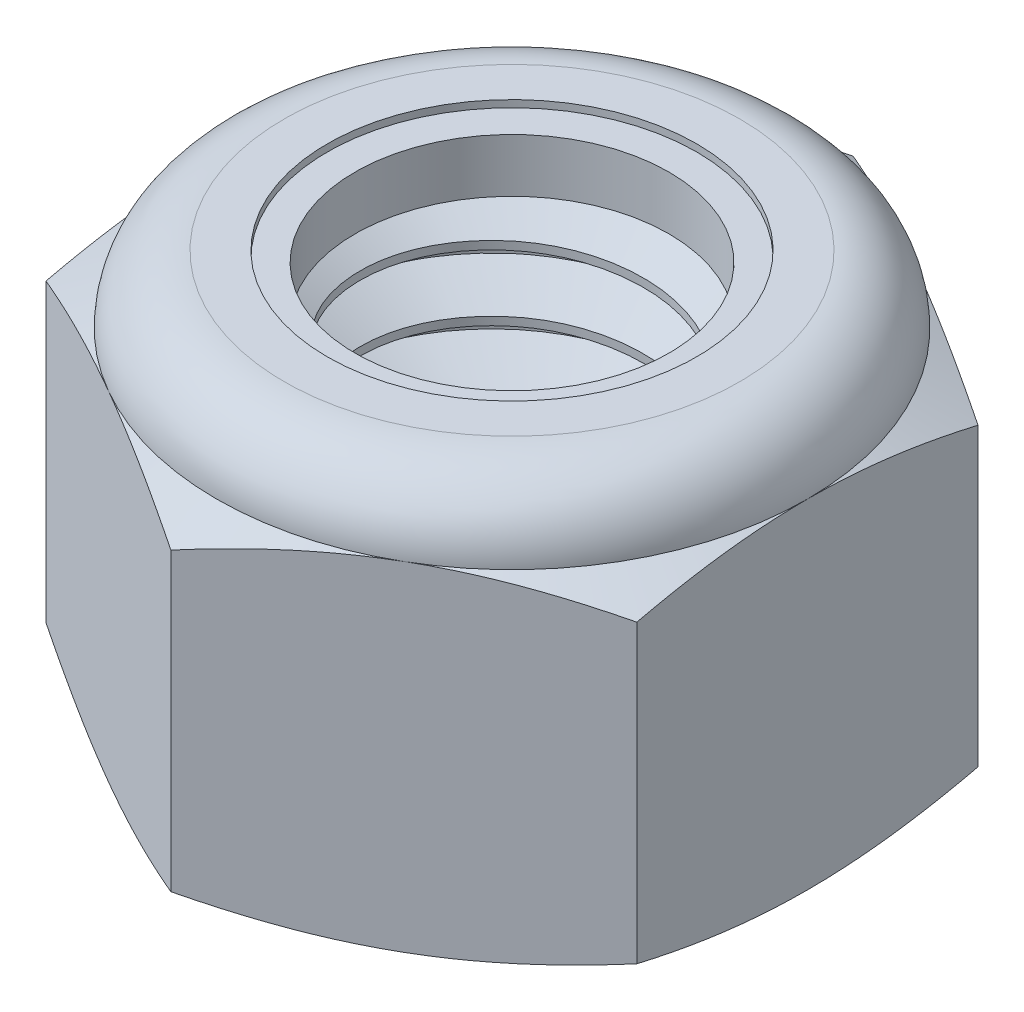
SolidWorks part; units mm, degrees
note: '?' marks a value the reader was unsure of.
ref_plane "Front" through (0, 0, 0) normal (0, 0, 1) x (1, 0, 0)
ref_plane "Top" through (0, 0, 0) normal (0, 1, 0) x (1, 0, 0)
ref_plane "Right" through (0, 0, 0) normal (1, 0, 0) x (0, 0, -1)
sketch "Sketch8" plane through (0, 0, 0) normal (1, 0, 0) x (0, 0, -1)
  line L0 (0, 0) -> (0, 8.7312) construction
  line L1 (6.35, 0) -> (-6.35, 0) construction
  line L2 (-3.9688, 8.7312) -> (3.9688, 8.7312) construction
  line L3 (3.9688, 8.7312) -> (3.9688, 7.3201) construction
sketch "Sketch1" plane through (0, 0, 0) normal (0, 1, 0) x (1, 0, 0)
  line L1 (0, 7.3323) -> (-6.35, 3.6662)
  line L2 (-6.35, 3.6662) -> (-6.35, -3.6662)
  line L3 (-6.35, -3.6662) -> (0, -7.3323)
  line L4 (0, -7.3323) -> (6.35, -3.6662)
  line L5 (6.35, -3.6662) -> (6.35, 3.6662)
  line L6 (6.35, 3.6662) -> (0, 7.3323)
  circle A0 centre (0, 0) radius 6.35 construction
  circle A1 centre (0, 0) radius 3.9688
extrude "Extrude1" add sketch "Sketch1" along normal up to vertex (8.7312 mm away) up to point (0, 8.7312, 0)
sketch "Sketch5" plane through (0, 0, 0) normal (1, 0, 0) x (0, 0, -1)
  line L0 (0, 0) -> (6.35, 0)
  line L1 (6.35, 0) -> (7.3323, 0.4581)
  line L2 (7.3323, 0.4581) -> (7.3323, 6.818)
  line L3 (7.3323, 6.818) -> (6.35, 7.276)
  line L4 (4.8948, 8.7312) -> (4.8948, 10.0012)
  line L5 (4.8948, 10.0012) -> (8.6023, 10.0012)
  line L6 (8.6023, 10.0012) -> (8.6023, -1.27)
  line L7 (8.6023, -1.27) -> (0, -1.27)
  line L8 (0, -1.27) -> (0, 0)
  line L9 (6.35, 7.276) -> (6.35, 0) construction
  line L12 (7.3323, 8.7312) -> (7.3323, 0) construction
  line L13 (7.3323, 4.3656) -> (8.6023, 4.3656) construction
  line L15 (0, 0) -> (0, 10.0012) construction
  line L18 (6.35, 0) -> (-6.35, 0) construction
  line L19 (3.6662, 8.7312) -> (7.3323, 8.7312) construction
  line L20 (0, 10.0012) -> (4.8948, 10.0012) construction
  line L21 (3.6662, 0) -> (7.3323, 0) construction
  arc A0 (6.35, 7.276) -> (4.8948, 8.7312) centre (4.8948, 7.276) ccw
  dimension "D1" = 25
  dimension "D2" = 1.27
  dimension "D4" = 1.4552
revolve "Cut-Revolve3" cut sketch "Sketch5" angle 360 about L15
sketch "Sketch4" plane through (0, 0, 0) normal (1, 0, 0) x (0, 0, -1)
  line L0 (0, 7.276) -> (4.3656, 7.276)
  line L1 (4.3656, 7.276) -> (0, 5.2403)
  line L3 (0, 2.0357) -> (4.3656, 0)
  line L4 (4.3656, 0) -> (0, 0)
  line L5 (0, 0) -> (0, 7.276) construction
  line L10 (0, 0) -> (0, 8.7312) construction
  line L11 (0, 2.0357) -> (0, 0)
  line L12 (0, 7.276) -> (0, 5.2403)
  line L13 (5.4993, 7.276) -> (0, 7.276) construction
  dimension "D1" = 25
  dimension "D2" = 8.7312
sketch "Sketch6" plane through (0, 0, 0) normal (1, 0, 0) x (0, 0, -1)
  line L0 (0, 7.276) -> (6.1976, 7.276)
  line L1 (4.8948, 8.5788) -> (2.4474, 8.5788)
  line L2 (0, 10.0012) -> (0, 7.276)
  line L3 (2.4474, 10.0012) -> (0, 10.0012)
  line L4 (0, 10.0012) -> (4.8948, 10.0012) construction
  line L5 (0, 0) -> (0, 10.0012) construction
  line L6 (0, 10.0012) -> (0, 0) construction
  line L7 (2.4474, 8.5788) -> (2.4474, 10.0012)
  line L8 (4.8948, 8.7312) -> (4.8948, 8.5788) construction
  line L9 (2.4474, 8.5788) -> (0, 8.5788) construction
  line L10 (0, 8.5788) -> (0, 5.2403) construction
  arc A0 (6.1976, 7.276) -> (4.8948, 8.5788) centre (4.8948, 7.276) ccw
  arc A1 (6.35, 7.276) -> (4.8948, 8.7312) centre (4.8948, 7.276) ccw construction
  dimension "D1" = 0.1524
revolve "Cut-Revolve4" cut sketch "Sketch6" angle 360 about L6
revolve "Cut-Revolve2" cut sketch "Sketch4" angle 360 about L5
sketch "Sketch7" plane through (0, 0, 0) normal (1, 0, 0) x (0, 0, -1)
  line L0 (3.3734, 7.3522) -> (6.119, 7.3522)
  line L1 (4.8948, 8.5026) -> (3.3734, 8.5026)
  line L2 (3.3734, 8.5026) -> (3.3734, 7.3522)
  line L3 (3.3734, 7.3522) -> (0, 7.3522) construction
  line L4 (0, 7.3522) -> (0, 8.5026) construction
  line L5 (0, 8.5026) -> (3.3734, 8.5026) construction
  line L6 (3.3734, 7.3522) -> (3.3734, 7.276) construction
  line L7 (0, 7.276) -> (6.1976, 7.276) construction
  line L8 (4.8948, 8.5026) -> (4.8948, 8.5788) construction
  arc A0 (6.119, 7.3522) -> (4.8948, 8.5026) centre (4.8948, 7.276) ccw
  arc A2 (6.1976, 7.276) -> (4.8948, 8.5788) centre (4.8948, 7.276) ccw construction
  dimension "D1" = 0.0762
  dimension "D2" = 6.7469
revolve "Revolve2" add sketch "Sketch7" angle 360 about L4
sketch "Sketch2" plane through (0, 0, 0) normal (1, 0, 0) x (0, 0, -1)
  line L0 (-3.9688, 0) -> (-3.9688, 7.276) construction
  line L1 (0, 0) -> (3.9688, 0)
  line L2 (0, 0) -> (0, 7.276)
  line L3 (0, 7.276) -> (3.9688, 7.276)
  line L4 (3.9688, 0) -> (3.9688, 7.276)
  line L6 (5.4993, 7.276) -> (6.35, 7.276) construction
  line L7 (0, -3.9688) -> (0, 0) construction
revolve "Revolve1" add sketch "Sketch2" angle 360 about L7
sketch "Sketch9" plane through (0, 0, 0) normal (1, 0, 0) x (0, 0, -1)
  line L0 (4.1215, 8.599) -> (4.1215, 7.1878) construction
  line L1 (4.1215, 7.1878) -> (2.8994, 7.8934) construction
  line L2 (2.8994, 7.8934) -> (4.1215, 8.599) construction
  line L3 (3.0522, 7.9816) -> (3.0522, 7.8052) construction
  line L4 (3.9688, 8.5108) -> (3.9688, 7.276) construction
  line L5 (2.8994, 7.8934) -> (3.0522, 7.8934) construction
  line L6 (3.9688, 7.8934) -> (4.1215, 7.8934) construction
  line L7 (4.0451, 7.8934) -> (4.0451, 8.5549) construction
  line L8 (4.1215, 7.1878) -> (4.0451, 8.5549)
  line L9 (4.0451, 8.5549) -> (3.0522, 7.9816)
  line L10 (3.0522, 7.9816) -> (3.0522, 7.8052)
  line L11 (3.0522, 7.8052) -> (4.1215, 7.1878)
  dimension "D1" = 1.4111
  dimension "D2" = 0.1764
sketch "Sketch10" plane through (0, 7.276, 0) normal (0, 1, 0) x (1, 0, 0)
  circle A1 centre (0, 0) radius 3.9688
  circle A2 centre (0, 0) radius 3.9688
  dimension "D1" = 0
curve "Helix/Spiral1" pitch 1.4111 height 10.1424 turns 7.1875
sweep "Cut-Sweep1" cut profiles "Sketch9" path "Helix/Spiral1" align with end faces yes
sketch "Sketch11" plane through (0, 0, 0) normal (1, 0, 0) x (0, 0, -1)
  line L0 (0, 0) -> (0, 8.7312) construction
  line L1 (6.35, 0) -> (-6.35, 0) construction
  line L4 (0, 8.7312) -> (0, 0) construction
  line L5 (0, 4.3656) -> (3.9688, 4.3656) construction
  line L6 (0, 0) -> (4.3656, 0)
  line L7 (0, 2.0357) -> (0, 0)
  line L8 (4.3656, 0) -> (0, 2.0357)
  dimension "D1" = 8.7312
  dimension "D2" = 25
revolve "Revolve3" add sketch "Sketch11" angle 360 about L4
sketch "Sketch12" plane through (0, 0, 0) normal (1, 0, 0) x (0, 0, -1)
  line L0 (4.3656, 7.276) -> (0, 7.276)
  line L1 (0, 7.276) -> (0, 0)
  line L2 (0, 0) -> (4.3656, 0)
  line L3 (6.35, 0) -> (-6.35, 0) construction
  line L4 (4.3656, 0) -> (4.3656, 7.276)
  line L5 (-4.3656, 0) -> (4.3656, 0) construction
revolve "Revolve4" add sketch "Sketch12" angle 360 about L0
combine bodies "Combine1" operation type subtract main body 136 bodies to subtract 133
ref_plane "Contact Plane 1" through (0, 0, 0) normal (0, -1, 0) x (1, 0, 0)
ref_axis "Center Axis 1" through (0, -2.1015, 0) along (0, 1, 0)?
equation "\"D4@Sketch5\"=\"Height@Sketch8\"/6"
equation "\"D1@Sketch9\"=\"Thread Pitch@Sketch8\""
equation "\"D2@Sketch9\"=\"Thread Pitch@Sketch8\"/8"
equation "\"D4@Helix/Spiral1\"=\"Thread Pitch@Sketch8\""
equation "\"D3@Helix/Spiral1\"=\"Thread Pitch@Sketch8\"+\"Height@Sketch8\""
equation "\"D2@Sketch4\"=\"Thread Dia@Sketch8\"*1.1"
equation "\"D1@Sketch11\"=\"Thread Dia@Sketch8\"*1.1"
equation "\"D2@Sketch7\"=\"Thread Dia@Sketch8\"*.85"
